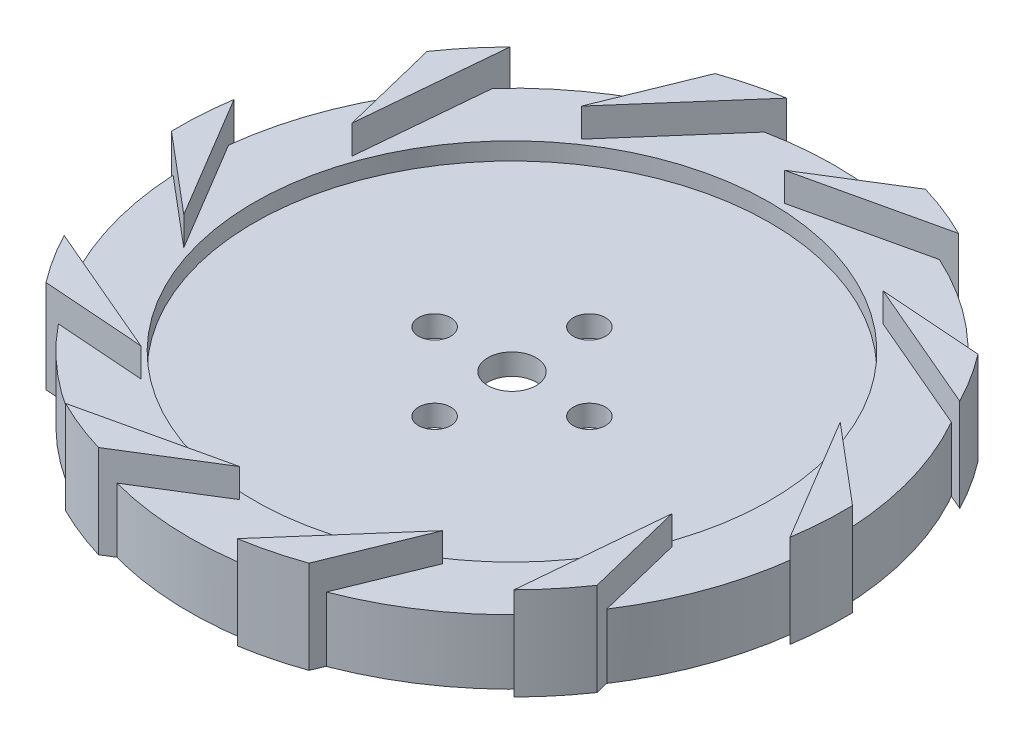
SolidWorks part; units mm, degrees
ref_plane "Front Plane" through (0, 0, 0) normal (0, 0, 1) x (1, 0, 0)
ref_plane "Top Plane" through (0, 0, 0) normal (0, 1, 0) x (1, 0, 0)
ref_plane "Right Plane" through (0, 0, 0) normal (1, 0, 0) x (0, 0, -1)
sketch "Sketch3" plane through (0, 0, 0) normal (0, 0, 1) x (1, 0, 0)
  line L0 (0, 0) -> (0, 40.1505) construction
  line L1 (-63.5, 16.0734) -> (-50.8, 16.0734)
  line L2 (-50.8, 16.0734) -> (-50.8, 12.6339)
  line L3 (-50.8, 12.6339) -> (0, 12.6339)
  line L4 (0, 12.6339) -> (0, 3.3734)
  line L5 (0, 3.3734) -> (-63.5, 3.3734)
  line L6 (-63.5, 3.3734) -> (-63.5, 16.0734)
  dimension "D1" = 12.7
  dimension "D2" = 63.5
  dimension "D3" = 50.8
revolve "Body" add sketch "Sketch3" angle 360 about L0
sketch "Sketch4" plane through (0, 0, 0) normal (0, 1, 0) x (1, 0, 0)
  line L0 (1.5533, 52.0769) -> (18.687, 62.7276)
  line L2 (29.4601, 58.4471) -> (1.5533, 52.0769)
  arc A0 (18.687, 62.7276) -> (29.4601, 58.4471) centre (0, 0) cw
extrude "Guide Vanes" add sketch "Sketch4" along direction (0, 1, 0) on the side of the normal blind 15.748 and the other way blind 2.54 from offset 5.969
pattern_circular "CirPattern4" count 10 over 360 about axis through (0, 16.0734, 0) along (0, -1, 0) of "Guide Vanes"
sketch "Sketch5" plane through (0, 3.3734, 0) normal (0, -1, 0) x (1, 0, 0)
  circle A0 centre (0, 0) radius 60.325
  dimension "D1" = 120.65
extrude "Hollow out" cut sketch "Sketch5" against normal blind 5.08 contours A0
sketch "Sketch6" plane through (0, 12.6339, 0) normal (0, 1, 0) x (1, 0, 0)
  circle A0 centre (0, 0) radius 4.7625
  dimension "D1" = 9.525
extrude "Cut-Extrude1" cut sketch "Sketch6" against normal through all
sketch "Sketch7" plane through (0, 12.6339, 0) normal (0, 1, 0) x (1, 0, 0)
  circle A0 centre (0, 15.24) radius 3.175
  circle A1 centre (0, 0) radius 4.7625 construction
  dimension "D1" = 6.35
  dimension "D2" = 15.24
extrude "Cut-Extrude2" cut sketch "Sketch7" against normal through all
pattern_circular "CirPattern5" count 4 over 360 about axis through (0, 12.6339, 0) along (0, 1, 0) of "Cut-Extrude2"
